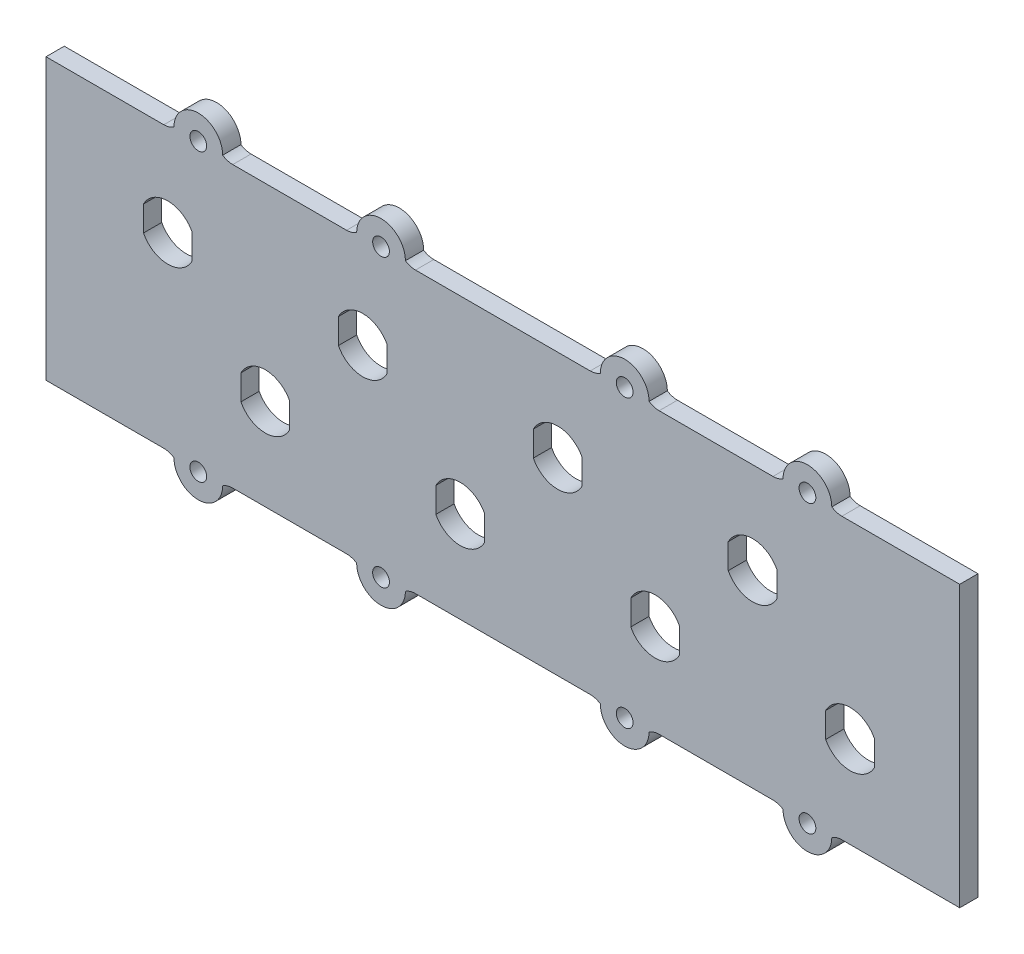
SolidWorks part; units mm, degrees
material "Aircraft Ply"
ref_plane "Front Plane" through (0, 0, 0) normal (0, 0, 1) x (1, 0, 0)
ref_plane "Top Plane" through (0, 0, 0) normal (0, 1, 0) x (1, 0, 0)
ref_plane "Right Plane" through (0, 0, 0) normal (1, 0, 0) x (0, 0, -1)
sketch "Sketch1" plane through (0, 0, 0) normal (0, 0, 1) x (1, 0, 0)
  line L0 (-75, 8) -> (75, 8) construction
  line L1 (-75, 0) -> (75, 0) construction
  line L8 (-75, 23) -> (-75, -23)
  line L9 (-44.3417, -23) -> (-25.6583, -23)
  line L10 (-14.3417, -23) -> (14.3417, -23)
  line L11 (25.6583, -23) -> (44.3417, -23)
  line L12 (75, -23) -> (75, 23)
  line L13 (44.3417, 23) -> (25.6583, 23)
  line L14 (14.3417, 23) -> (-14.3417, 23)
  line L15 (-25.6583, 23) -> (-44.3417, 23)
  line L16 (-75, 23) -> (-75, -23)
  line L17 (-44.3417, -23) -> (-25.6583, -23)
  line L18 (-14.3417, -23) -> (14.3417, -23)
  line L19 (25.6583, -23) -> (44.3417, -23)
  line L20 (75, -23) -> (75, 23)
  line L21 (44.3417, 23) -> (25.6583, 23)
  line L22 (14.3417, 23) -> (-14.3417, 23)
  line L23 (-25.6583, 23) -> (-44.3417, 23)
  line L30 (-75, -23) -> (-55.6583, -23)
  line L31 (-75, -23) -> (-55.6583, -23)
  line L32 (55.6583, -23) -> (75, -23)
  line L33 (55.6583, -23) -> (75, -23)
  line L34 (75, 23) -> (55.6583, 23)
  line L35 (75, 23) -> (55.6583, 23)
  line L36 (-55.6583, 23) -> (-75, 23)
  line L37 (-55.6583, 23) -> (-75, 23)
  line L38 (-51, 10.0616) -> (-51, 5.9384)
  line L39 (-59, 10.0616) -> (-59, 5.9384)
  line L40 (-27, 10.0616) -> (-27, 5.9384)
  line L41 (-19, 10.0616) -> (-19, 5.9384)
  line L42 (5, 10.0616) -> (5, 5.9384)
  line L43 (13, 10.0616) -> (13, 5.9384)
  line L44 (37, 10.0616) -> (37, 5.9384)
  line L45 (45, 10.0616) -> (45, 5.9384)
  line L46 (-11, -5.9384) -> (-11, -10.0616)
  line L47 (-3, -5.9384) -> (-3, -10.0616)
  line L48 (21, -5.9384) -> (21, -10.0616)
  line L49 (29, -5.9384) -> (29, -10.0616)
  line L50 (53, -5.9384) -> (53, -10.0616)
  line L51 (61, -5.9384) -> (61, -10.0616)
  line L52 (-43, -5.9384) -> (-43, -10.0616)
  line L53 (-35, -5.9384) -> (-35, -10.0616)
  circle A0 centre (-50, 23.5) radius 1.375 construction
  circle A1 centre (-20, 23.5) radius 1.375 construction
  circle A2 centre (20, 23.5) radius 1.375 construction
  circle A3 centre (50, 23.5) radius 1.375 construction
  circle A4 centre (50, -23.5) radius 1.375 construction
  circle A5 centre (20, -23.5) radius 1.375 construction
  circle A6 centre (-20, -23.5) radius 1.375 construction
  circle A7 centre (-50, -23.5) radius 1.375 construction
  circle A8 centre (-50, -23.5) radius 1.375
  circle A9 centre (-20, -23.5) radius 1.375
  circle A10 centre (20, -23.5) radius 1.375
  circle A11 centre (50, -23.5) radius 1.375
  circle A12 centre (50, 23.5) radius 1.375
  circle A13 centre (20, 23.5) radius 1.375
  circle A14 centre (-20, 23.5) radius 1.375
  circle A15 centre (-50, 23.5) radius 1.375
  circle A16 centre (-55, 8) radius 4.5
  circle A17 centre (-23, 8) radius 4.5
  circle A18 centre (9, 8) radius 4.5
  circle A19 centre (41, 8) radius 4.5
  circle A20 centre (-39, -8) radius 4.5
  circle A21 centre (-7, -8) radius 4.5
  circle A22 centre (25, -8) radius 4.5
  circle A23 centre (57, -8) radius 4.5
  arc A29 (-54, -23.5) -> (-55.6583, -23) centre (-55.6583, -26) ccw
  arc A30 (-54, -23.5) -> (-46, -23.5) centre (-50, -23.5) ccw
  arc A31 (-44.3417, -23) -> (-46, -23.5) centre (-44.3417, -26) ccw
  arc A32 (-24, -23.5) -> (-25.6583, -23) centre (-25.6583, -26) ccw
  arc A33 (-24, -23.5) -> (-16, -23.5) centre (-20, -23.5) ccw
  arc A34 (-14.3417, -23) -> (-16, -23.5) centre (-14.3417, -26) ccw
  arc A35 (16, -23.5) -> (14.3417, -23) centre (14.3417, -26) ccw
  arc A36 (16, -23.5) -> (24, -23.5) centre (20, -23.5) ccw
  arc A37 (25.6583, -23) -> (24, -23.5) centre (25.6583, -26) ccw
  arc A38 (46, -23.5) -> (44.3417, -23) centre (44.3417, -26) ccw
  arc A39 (46, -23.5) -> (54, -23.5) centre (50, -23.5) ccw
  arc A40 (55.6583, -23) -> (54, -23.5) centre (55.6583, -26) ccw
  arc A43 (54, 23.5) -> (55.6583, 23) centre (55.6583, 26) ccw
  arc A44 (54, 23.5) -> (46, 23.5) centre (50, 23.5) ccw
  arc A45 (44.3417, 23) -> (46, 23.5) centre (44.3417, 26) ccw
  arc A46 (24, 23.5) -> (25.6583, 23) centre (25.6583, 26) ccw
  arc A47 (24, 23.5) -> (16, 23.5) centre (20, 23.5) ccw
  arc A48 (14.3417, 23) -> (16, 23.5) centre (14.3417, 26) ccw
  arc A49 (-16, 23.5) -> (-14.3417, 23) centre (-14.3417, 26) ccw
  arc A50 (-16, 23.5) -> (-24, 23.5) centre (-20, 23.5) ccw
  arc A51 (-25.6583, 23) -> (-24, 23.5) centre (-25.6583, 26) ccw
  arc A52 (-46, 23.5) -> (-44.3417, 23) centre (-44.3417, 26) ccw
  arc A53 (-46, 23.5) -> (-54, 23.5) centre (-50, 23.5) ccw
  arc A54 (-55.6583, 23) -> (-54, 23.5) centre (-55.6583, 26) ccw
  arc A57 (-54, -23.5) -> (-55.6583, -23) centre (-55.6583, -26) ccw
  arc A58 (-54, -23.5) -> (-46, -23.5) centre (-50, -23.5) ccw
  arc A59 (-44.3417, -23) -> (-46, -23.5) centre (-44.3417, -26) ccw
  arc A60 (-24, -23.5) -> (-25.6583, -23) centre (-25.6583, -26) ccw
  arc A61 (-24, -23.5) -> (-16, -23.5) centre (-20, -23.5) ccw
  arc A62 (-14.3417, -23) -> (-16, -23.5) centre (-14.3417, -26) ccw
  arc A63 (16, -23.5) -> (14.3417, -23) centre (14.3417, -26) ccw
  arc A64 (16, -23.5) -> (24, -23.5) centre (20, -23.5) ccw
  arc A65 (25.6583, -23) -> (24, -23.5) centre (25.6583, -26) ccw
  arc A66 (46, -23.5) -> (44.3417, -23) centre (44.3417, -26) ccw
  arc A67 (46, -23.5) -> (54, -23.5) centre (50, -23.5) ccw
  arc A68 (55.6583, -23) -> (54, -23.5) centre (55.6583, -26) ccw
  arc A71 (54, 23.5) -> (55.6583, 23) centre (55.6583, 26) ccw
  arc A72 (54, 23.5) -> (46, 23.5) centre (50, 23.5) ccw
  arc A73 (44.3417, 23) -> (46, 23.5) centre (44.3417, 26) ccw
  arc A74 (24, 23.5) -> (25.6583, 23) centre (25.6583, 26) ccw
  arc A75 (24, 23.5) -> (16, 23.5) centre (20, 23.5) ccw
  arc A76 (14.3417, 23) -> (16, 23.5) centre (14.3417, 26) ccw
  arc A77 (-16, 23.5) -> (-14.3417, 23) centre (-14.3417, 26) ccw
  arc A78 (-16, 23.5) -> (-24, 23.5) centre (-20, 23.5) ccw
  arc A79 (-25.6583, 23) -> (-24, 23.5) centre (-25.6583, 26) ccw
  arc A80 (-46, 23.5) -> (-44.3417, 23) centre (-44.3417, 26) ccw
  arc A81 (-46, 23.5) -> (-54, 23.5) centre (-50, 23.5) ccw
  arc A82 (-55.6583, 23) -> (-54, 23.5) centre (-55.6583, 26) ccw
  dimension "D2" = 9
  dimension "D3" = 8
  dimension "D6" = 20
  dimension "D7" = 8
  dimension "D1" = 0
  dimension "D4" = 4
  dimension "D5" = 2
extrude "Boss-Extrude1" add sketch "Sketch1" along normal blind 3 contours A82 L37 L16 L31 A57 A58 A59 L17 A60 A61 A62 L18 A63 A64 A65 L19 A66 A67 A68 L33 L20 L35 A71 A72 A73 L21 A74 A75 A76 L22 A77 A78 A79 L23 A80 A81 A23 A22 A21 | L39 A16 | L38 A16 | L40 A17 | L41 A17 | L42 A18 | L43 A18 | L44 A19 | L45 A19 | L50 A23 | L51 A23 | L48 A22 | L49 A22 | L46 A21 | L47 A21 | L52 A20 | L53 A20 region at (-0.0773, 0, 0) region at (-50.799, 8, 0) region at (-59.201, 8, 0) region at (-27.201, 8, 0) region at (-18.799, 8, 0) region at (4.799, 8, 0) region at (13.201, 8, 0) region at (36.799, 8, 0) region at (45.201, 8, 0) region at (-11.201, -8, 0) region at (-2.799, -8, 0) region at (20.799, -8, 0) region at (29.201, -8, 0) region at (52.799, -8, 0) region at (61.201, -8, 0) region at (-43.201, -8, 0) region at (-34.799, -8, 0)
sketch "Sketch2" plane through (0, 0, 3) normal (0, 0, 1) x (1, 0, 0)
  line L0 (-55, 8) -> (-39, -8) construction
  line L1 (-48.3527, 14.6473) -> (-32.3527, -1.3527)
  line L2 (-61.6473, 1.3527) -> (-45.6473, -14.6473)
  line L3 (-23, 8) -> (-7, -8) construction
  line L4 (-16.3527, 14.6473) -> (-0.3527, -1.3527)
  line L5 (-29.6473, 1.3527) -> (-13.6473, -14.6473)
  line L6 (25, -8) -> (9, 8) construction
  line L7 (18.3527, -14.6473) -> (2.3527, 1.3527)
  line L8 (31.6473, -1.3527) -> (15.6473, 14.6473)
  line L9 (41, 8) -> (57, -8) construction
  line L10 (47.6473, 14.6473) -> (63.6473, -1.3527)
  line L11 (34.3527, 1.3527) -> (50.3527, -14.6473)
  arc A10 (-48.3527, 14.6473) -> (-61.6473, 1.3527) centre (-55, 8) ccw
  arc A11 (-45.6473, -14.6473) -> (-32.3527, -1.3527) centre (-39, -8) ccw
  arc A12 (-16.3527, 14.6473) -> (-29.6473, 1.3527) centre (-23, 8) ccw
  arc A13 (-13.6473, -14.6473) -> (-0.3527, -1.3527) centre (-7, -8) ccw
  arc A14 (18.3527, -14.6473) -> (31.6473, -1.3527) centre (25, -8) ccw
  arc A15 (15.6473, 14.6473) -> (2.3527, 1.3527) centre (9, 8) ccw
  arc A16 (47.6473, 14.6473) -> (34.3527, 1.3527) centre (41, 8) ccw
  arc A17 (50.3527, -14.6473) -> (63.6473, -1.3527) centre (57, -8) ccw
  text T0 "      1" font "Century Gothic" height in points 18
  point P2 (-47, 0)
  point P7 (-15, 0)
  point P14 (17, 0)
  point P21 (49, 0)
